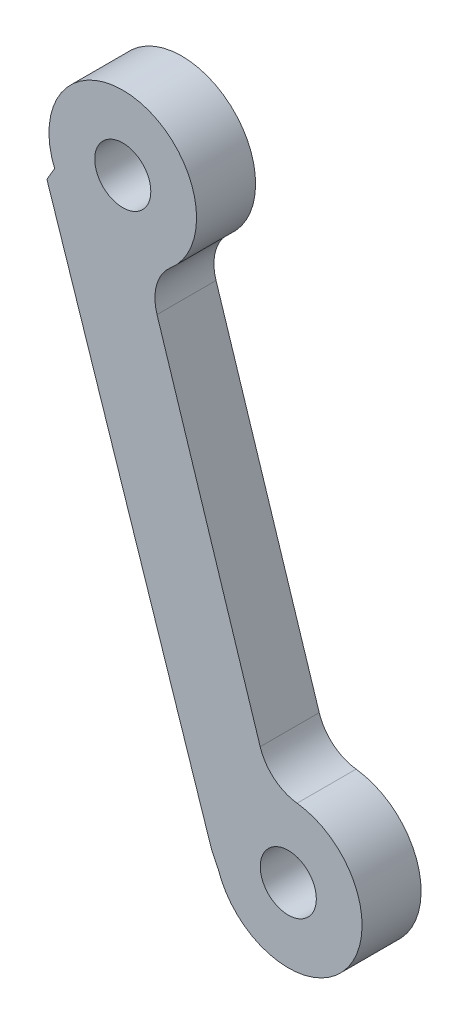
SolidWorks part; units mm, degrees
ref_plane "Front Plane" through (0, 0, 0) normal (0, 0, 1) x (1, 0, 0)
ref_plane "Top Plane" through (0, 0, 0) normal (0, 1, 0) x (1, 0, 0)
ref_plane "Right Plane" through (0, 0, 0) normal (1, 0, 0) x (0, 0, -1)
sketch "Sketch1" plane through (0, 0, 0) normal (0, 0, 1) x (1, 0, 0)
  line L0 (124.38, 516.941) -> (697.7134, 516.941) construction
  line L7 (15.0111, 49.8307) -> (3.8387, 83.6229)
  line L10 (10.5731, 81.687) -> (18.8981, 55.6504)
  line L13 (3.8387, 83.6229) -> (4.3612, 84.5098)
  line L16 (18.8981, 55.6504) -> (18.9693, 55.369)
  line L17 (15.0111, 49.8307) -> (15.4551, 48.9286)
  circle A7 centre (8.9794, 86.4262) radius 1.9
  circle A8 centre (20.1946, 50.5214) radius 1.9
  arc A9 (10.5731, 81.687) -> (4.3612, 84.5098) centre (8.9794, 86.4262) ccw
  arc A11 (15.4551, 48.9286) -> (18.9693, 55.369) centre (20.1946, 50.5214) ccw
extrude "Boss-Extrude1" add sketch "Sketch1" along normal blind 4
fillet "Fillet2" radius 3 2 edges at (18.9693, 55.369, 2) (10.5731, 81.687, 2)
